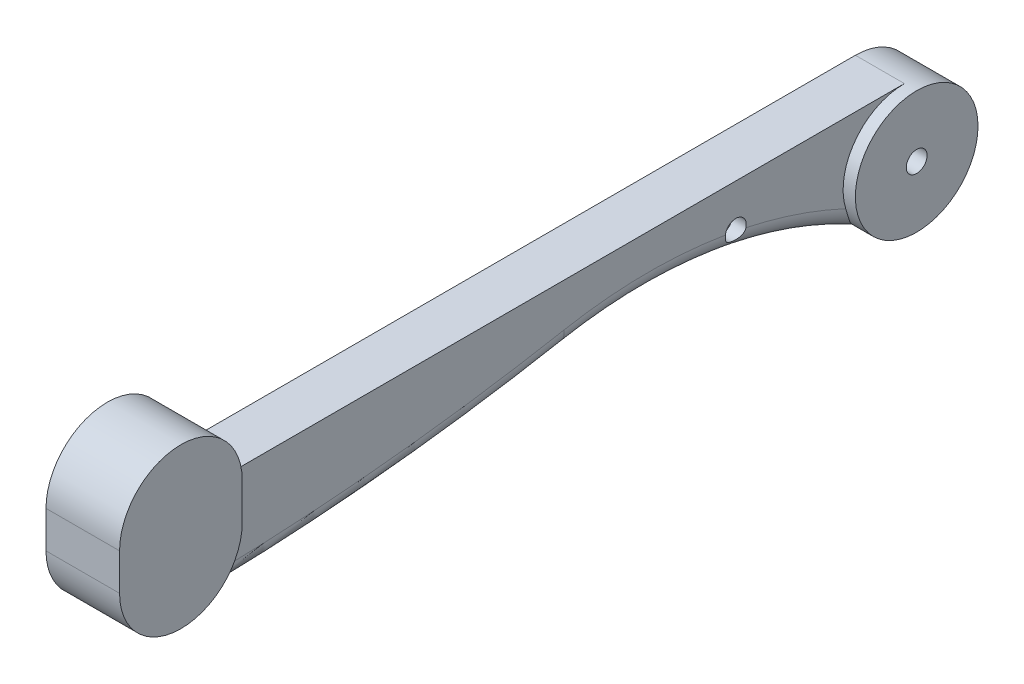
SolidWorks part; units mm, degrees
ref_plane "Front Plane" through (0, 0, 0) normal (0, 0, 1) x (1, 0, 0)
ref_plane "Top Plane" through (0, 0, 0) normal (0, 1, 0) x (1, 0, 0)
ref_plane "Right Plane" through (0, 0, 0) normal (1, 0, 0) x (0, 0, -1)
sketch "Sketch1" plane through (0, 0, 0) normal (1, 0, 0) x (0, 0, -1)
  line L0 (0, 10) -> (-110, 10)
  line L1 (-130, 10) -> (-130, 4)
  arc A0 (0, 10) -> (-5.0267, -8.6448) centre (0, 0) cw
  arc A1 (-110, 10) -> (-130, 10) centre (-120, 10) ccw
  arc A2 (-130, 4) -> (-120, -6) centre (-120, 4) ccw
  arc A3 (-120, -6) -> (-55, 0) centre (-120, 349.0833) ccw
  arc A4 (-55, 0) -> (-5.0267, -8.6448) centre (-41.6595, -71.6456) cw
  circle A5 centre (0, 0) radius 1.7
  point P0 (0, 0)
  point P19 (-55, 10)
  dimension "D1" = 10
  dimension "D4" = 10
  dimension "D5" = 3.4
  dimension "D2" = 130
  dimension "D3" = 6
extrude "Boss-Extrude1" add sketch "Sketch1" along normal mid plane 8
sketch "Sketch2" plane through (0, 0, 0) normal (1, 0, 0) x (0, 0, -1)
  line L0 (-130, 10) -> (-130, 4) construction
  line L1 (-130, 4) -> (-130, 10)
  line L2 (-110, 4) -> (-110, 10)
  arc A0 (-110, 10) -> (-130, 10) centre (-120, 10) ccw
  arc A1 (-130, 4) -> (-110, 4) centre (-120, 4) ccw
extrude "Boss-Extrude2" add sketch "Sketch2" along normal mid plane 12
sketch "Sketch3" plane through (0, 0, 0) normal (1, 0, 0) x (0, 0, -1)
  circle A0 centre (0, 0) radius 10
extrude "Boss-Extrude3" add sketch "Sketch3" along normal blind 6
fillet "Fillet2" radius 3 4 edges at (4, -4.4968, 87.3618) (-4, -4.4968, 87.3618) (4, 0.1649, 29.2371) (-4, 0.1649, 29.2371) tangent propagation no
extrude "Cut-Extrude1" cut sketch "Sketch1<2>" along normal through all contours A5 region at (0, 0, 0)
sketch "Sketch1<2>" plane through (0, 0, 0) normal (1, 0, 0) x (0, 0, -1) same geometry as "Sketch1"
sketch "Sketch5" plane through (0, 0, 0) normal (1, 0, 0) x (0, 0, -1)
  line L0 (0, 10) -> (-110, 10) construction
  line L1 (-32.1985, 4.7101) -> (-33.6262, 0.7873)
  line L2 (-22.6704, 4.2941) -> (-21.0528, -1.7426)
  line L3 (-33.6262, 0.7873) -> (-21.0528, -1.7426)
  line L4 (-27.5, -7.2828) -> (-27.5, 15.3934) construction
  arc A0 (-32.1985, 4.7101) -> (-22.6704, 4.2941) centre (-27.5, 3) cw
  arc A1 (-5.0267, -8.6448) -> (-55, 0) centre (-41.6595, -71.6456) ccw construction
  point P0 (-27.5, 3)
  point P13 (-27.5, 3)
  point P15 (-33.1961, 0.7383)
  dimension "D3" = 5
  dimension "D1" = 27.5
  dimension "D2" = 7
  dimension "D4" = 15
  dimension "D5" = 20
extrude "Cut-Extrude3" cut sketch "Sketch5" against normal mid plane 3.4
sketch "Sketch9" plane through (0, 0, 0) normal (1, 0, 0) x (0, 0, -1)
  circle A0 centre (-27.5, 3) radius 1.7
  dimension "D1" = 3.4
extrude "Cut-Extrude4" cut sketch "Sketch9" against normal through all both and the other way through all
